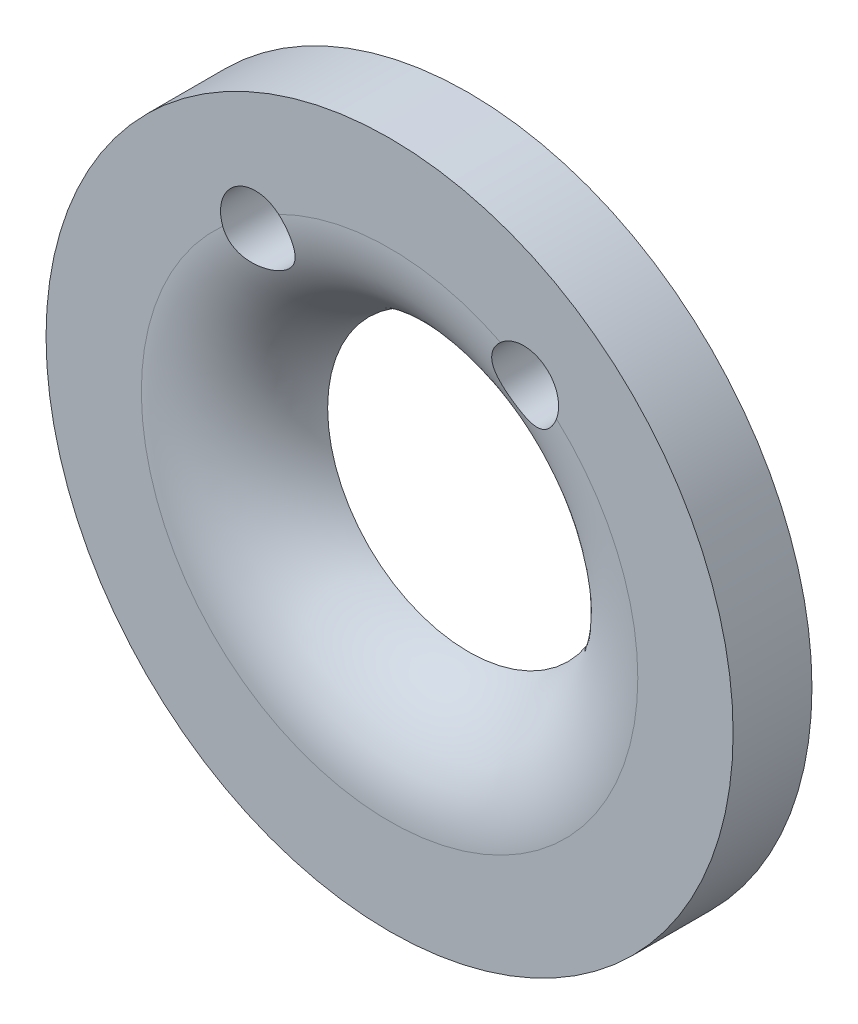
SolidWorks part; units mm, degrees
ref_plane "Front Plane" through (0, 0, 0) normal (1, 0, 0) x (0, 1, 0)
ref_plane "Top Plane" through (0, 0, 0) normal (0, 0, 1) x (0, 1, 0)
ref_plane "Right Plane" through (0, 0, 0) normal (0, 1, 0) x (-1, 0, 0)
sketch "Sketch1" plane through (0, 0, 0) normal (0, 0, 1) x (0, 1, 0)
  circle A0 centre (0, 0) radius 30.5
  dimension "D1" = 61
extrude "Boss-Extrude1" add sketch "Sketch1" along normal blind 7
sketch "Sketch2" plane through (0, 0, 7) normal (0, 0, 1) x (1, 0, 0)
  line L0 (0, 30.5) -> (0, -30.5) construction
  line L2 (-8.8074, 17.3944) -> (8.8074, 17.3944)
  circle A0 centre (0, 0) radius 30.5 construction
  circle A2 centre (-11.9074, 17.3944) radius 3.1
  circle A3 centre (11.9074, 17.3944) radius 3.1
  circle A4 centre (0, 0) radius 12.5
  point P10 (0, 17.3944)
  dimension "D1" = 6.2
  dimension "D2" = 25
extrude "2x 6.2 mm and 25 mm thru" cut sketch "Sketch2" against normal through all contours A4 L0 | L0 A4 | A2 | A3 region at (5.3052, 0, 7) region at (-5.3052, 0, 7) region at (-11.9074, 17.3944, 7) region at (11.9074, 17.3944, 7)
fillet "10mm filet" radius 10 1 edges at (12.5, 0, 7)
